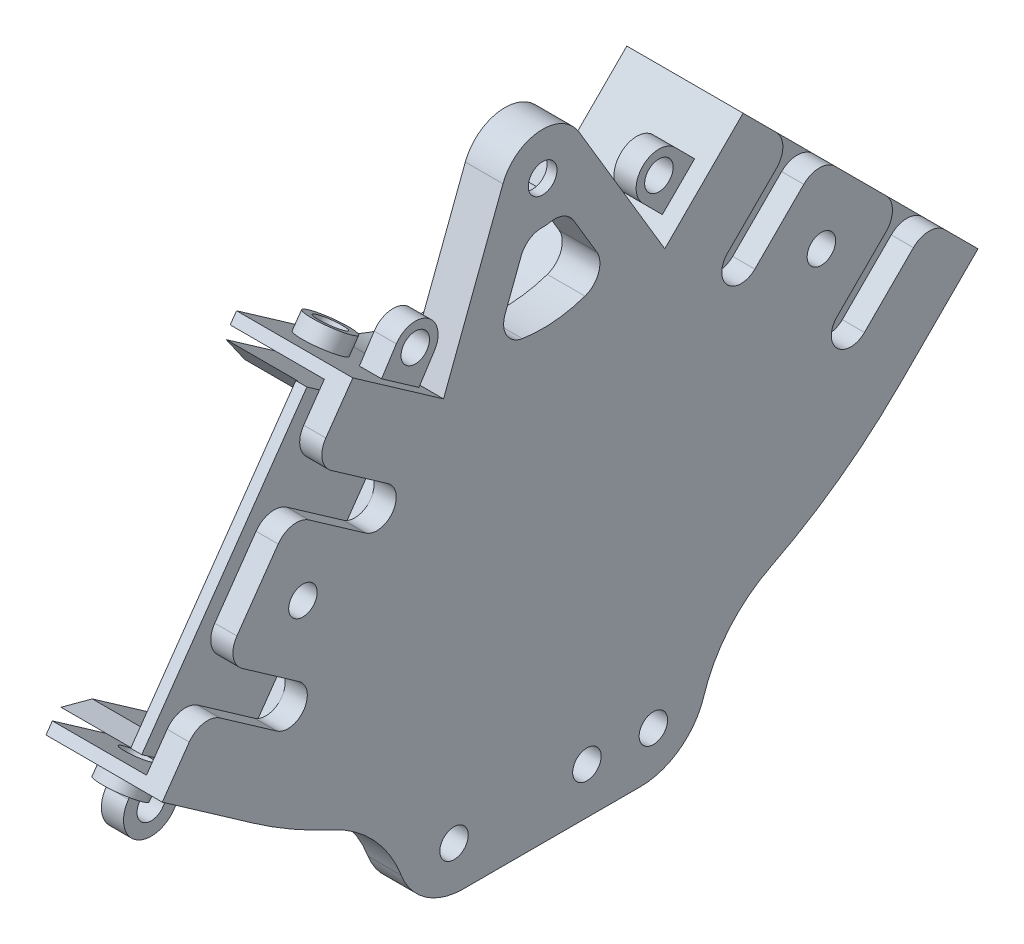
SolidWorks part; units mm, degrees
ref_plane "Front Plane" through (0, 0, 0) normal (0, 0, 1) x (1, 0, 0)
ref_plane "Top Plane" through (0, 0, 0) normal (0, 1, 0) x (1, 0, 0)
ref_plane "Right Plane" through (0, 0, 0) normal (1, 0, 0) x (0, 0, -1)
sketch "Sketch3" plane through (0, 0, 0) normal (1, 0, 0) x (0, 0, -1)
  line L0 (-22.7274, -32.4581) -> (-62.0633, -88.6355)
  line L1 (28.0184, -28.0184) -> (76.5118, -76.5118)
  line L2 (-22.7274, -32.4581) -> (0, 0) construction
  line L3 (0, 0) -> (28.0184, -28.0184) construction
  line L4 (0, 40.513) -> (0, -40.513) construction
  line L5 (-62.0633, -88.6355) -> (-66.4339, -94.8775)
  line L6 (76.5118, -76.5118) -> (81.8999, -81.8999)
  arc A2 (-62.0633, -88.6355) -> (76.5118, -76.5118) centre (0, 0) ccw
  arc A4 (-27.098, -38.7) -> (33.4066, -33.4066) centre (0, 0) ccw
  arc A5 (-22.7274, -32.4581) -> (28.0184, -28.0184) centre (0, 0) ccw
  arc A6 (-66.4339, -94.8775) -> (81.8999, -81.8999) centre (0, 0) ccw
  dimension "D1" = 216.408
  dimension "D2" = 135
  dimension "D3" = 94.488
  dimension "D4" = 7.62
  dimension "D6" = 7.62
  dimension "D5" = 80
extrude "Base extrude" add sketch "Sketch3" along normal blind 58.42 contours L5 A6 L6 A2 | A5 L0 A4 L1 region at (0, -39.9408, -3.4944) region at (0, -109.321, -9.5643)
sketch "Sketch4" plane through (58.42, 0, 0) normal (1, 0, 0) x (0, 0, -1)
  line L0 (-66.4339, -94.8775) -> (-22.7274, -32.4581)
  line L1 (28.0184, -28.0184) -> (81.8999, -81.8999)
  arc A0 (-22.7274, -32.4581) -> (28.0184, -28.0184) centre (0, 0) ccw
  arc A1 (-22.7274, -32.4581) -> (28.0184, -28.0184) centre (0, 0) ccw construction
  arc A2 (-66.4339, -94.8775) -> (81.8999, -81.8999) centre (0, 0) ccw
  arc A3 (-66.4339, -94.8775) -> (81.8999, -81.8999) centre (0, 0) ccw construction
  arc M1 (28.0184, -28.0184) -> (-22.7274, -32.4581) centre (0, 0) cw
  line M2 (-22.7274, -32.4581) -> (-27.098, -38.7)
  arc M3 (-27.098, -38.7) -> (33.4066, -33.4066) centre (0, 0) ccw
  line M4 (33.4066, -33.4066) -> (28.0184, -28.0184)
extrude "Outer wall" add sketch "Sketch4" along normal blind 7.62 contours L0 A2 L1 M3 | M4 M1 M2 M3 region at (58.42, -79.1939, -6.9286) region at (58.42, -39.9408, -3.4944)
ref_plane "Midplane" through (29.21, 0, 0) normal (-1, 0, 0) x (0, 0, 1)
mirror "Mirror1" about plane through (29.21, 0, 0) normal (-1, 0, 0) of "Outer wall"
sketch "Sketch6" plane through (0, 0, 0) normal (0, 0.5736, 0.8192) x (1, 0, 0)
  line L27 (-5.08, -42.164) -> (63.5, -42.164)
  line L28 (-5.08, -42.164) -> (-5.08, -113.284)
  line L29 (-5.08, -113.284) -> (63.5, -113.284)
  line L30 (63.5, -42.164) -> (63.5, -113.284)
  line L31 (-2.54, -44.704) -> (60.96, -44.704)
  line L32 (-2.54, -44.704) -> (-2.54, -110.744)
  line L33 (-2.54, -110.744) -> (60.96, -110.744)
  line L34 (60.96, -44.704) -> (60.96, -110.744)
  line L35 (58.42, -47.244) -> (0, -47.244) construction
  line L36 (0, -108.204) -> (0, -18.7894) construction
  line L37 (58.42, -18.7894) -> (58.42, -108.204) construction
  line L38 (58.42, -108.204) -> (0, -108.204) construction
  line L40 (0, -47.244) -> (58.42, -47.244)
  line L41 (0, -47.244) -> (0, -108.204)
  line L42 (0, -108.204) -> (58.42, -108.204)
  line L43 (58.42, -47.244) -> (58.42, -108.204)
  line L44 (-7.62, -39.624) -> (66.04, -39.624)
  line L45 (-7.62, -39.624) -> (-7.62, -115.824)
  line L46 (-7.62, -115.824) -> (66.04, -115.824)
  line L47 (66.04, -39.624) -> (66.04, -115.824)
  line M21 (-7.62, -39.624) -> (-7.62, -115.824)
  line M22 (-7.62, -115.824) -> (66.04, -115.824)
  line M23 (66.04, -115.824) -> (66.04, -39.624)
  line M24 (66.04, -39.624) -> (-7.62, -39.624)
  line M25 (58.42, -108.204) -> (0, -108.204)
  line M26 (0, -108.204) -> (0, -47.244)
  line M27 (0, -47.244) -> (58.42, -47.244)
  line M28 (58.42, -47.244) -> (58.42, -108.204)
  dimension "D1" = 2.54
  dimension "D2" = 2.54
  dimension "D3" = 2.54
  dimension "D4" = 2.54
  dimension "D5" = 2.54
  dimension "D6" = 2.54
  dimension "D7" = 2.54
  dimension "D8" = 2.54
extrude "Endcap 1" add sketch "Sketch6" along normal blind 25.4 contours L27 L30 L29 L28 M24 M21 M22 M23 | L34 L31 L32 L33 M28 M25 M26 M27 region at (29.21, -37.3698, 26.1667) region at (29.21, -33.3262, 23.3353)
sketch "Sketch7" plane through (0, 0, 0) normal (0, 0.7071, -0.7071) x (1, 0, 0)
  line L0 (-5.08, 113.284) -> (63.5, 113.284)
  line L1 (-5.08, 113.284) -> (-5.08, 42.164)
  line L2 (-5.08, 42.164) -> (63.5, 42.164)
  line L3 (63.5, 113.284) -> (63.5, 42.164)
  line L4 (-2.54, 110.744) -> (60.96, 110.744)
  line L5 (-2.54, 110.744) -> (-2.54, 44.704)
  line L6 (-2.54, 44.704) -> (60.96, 44.704)
  line L7 (60.96, 110.744) -> (60.96, 44.704)
  line L8 (0, 108.204) -> (58.42, 108.204)
  line L9 (0, 108.204) -> (0, 47.244)
  line L10 (0, 47.244) -> (58.42, 47.244)
  line L11 (58.42, 108.204) -> (58.42, 47.244)
  line L12 (-7.62, 115.824) -> (66.04, 115.824)
  line L13 (-7.62, 115.824) -> (-7.62, 39.624)
  line L14 (-7.62, 39.624) -> (66.04, 39.624)
  line L15 (66.04, 115.824) -> (66.04, 39.624)
  line L16 (58.42, 108.204) -> (0, 108.204) construction
  line L17 (58.42, 47.244) -> (58.42, 108.204) construction
  line L18 (66.04, 115.824) -> (-7.62, 115.824) construction
  line L19 (66.04, 39.624) -> (66.04, 115.824) construction
  line L20 (-7.62, 39.624) -> (-7.62, 115.824) construction
  line L21 (66.04, 39.624) -> (-7.62, 39.624) construction
  line M17 (66.04, 115.824) -> (-7.62, 115.824)
  line M18 (-7.62, 115.824) -> (-7.62, 39.624)
  line M19 (-7.62, 39.624) -> (66.04, 39.624)
  line M20 (66.04, 39.624) -> (66.04, 115.824)
  line M21 (0, 47.244) -> (0, 108.204)
  line M22 (0, 108.204) -> (58.42, 108.204)
  line M23 (58.42, 108.204) -> (58.42, 47.244)
  line M24 (58.42, 47.244) -> (0, 47.244)
  dimension "D1" = 2.54
  dimension "D2" = 2.54
  dimension "D3" = 2.54
  dimension "D4" = 2.54
  dimension "D5" = 2.54
  dimension "D6" = 2.54
  dimension "D7" = 2.54
  dimension "D8" = 2.54
extrude "Endcap 2" add sketch "Sketch7" along normal blind 25.4 contours L0 L3 L2 L1 M20 M17 M18 M19 | L7 L4 L5 L6 M24 M21 M22 M23 region at (29.21, -77.66, -77.66) region at (29.21, -81.1505, -81.1505)
chamfer "Internal Chamfer" distance 7.62 angle 20 4 edges at (29.21, -74.0667, 82.8697) (29.21, -24.1312, 47.9045) (29.21, -58.5513, -94.4723) (29.21, -15.446, -51.3671) first distance on face at (29.21, -81.3511, 72.4665) first distance on face at (29.21, -31.4156, 37.5013) first distance on face at (29.21, -67.5315, -85.492) first distance on face at (29.21, -24.4263, -42.3868)
ref_plane "Plane2" through (0, -13.9736, -1.2225) normal (0, -0.9962, -0.0872) x (-1, 0, 0)
sketch "Sketch10" plane through (0, -13.9736, -1.2225) normal (0, -0.9962, -0.0872) x (-1, 0, 0)
  line L0 (-66.04, 93.9078) -> (7.62, 93.9078) construction
  line L1 (-16.51, 95.5358) -> (-41.91, 95.5358)
  line L2 (-16.51, 95.5358) -> (-16.51, -82.1857)
  line L3 (-16.51, -82.1857) -> (-41.91, -82.1857)
  line L4 (-41.91, 95.5358) -> (-41.91, -82.1857)
  point P4 (-29.21, 93.9078)
  point P5 (-29.21, 95.5358)
  dimension "D1" = 25.4
extrude "Flywheel Hole" cut sketch "Sketch10" along normal up to next
sketch "Sketch11" plane through (-7.62, 0, 0) normal (-1, 0, 0) x (0, 0, 1)
  line L0 (-25.2982, 2.2719) -> (-28.0184, -28.0184)
  line L4 (-3.0636, -22.3183) -> (-4.5937, -39.3568)
  line L5 (6.8995, -21.445) -> (11.3704, -37.9575)
  line L6 (-20.4217, -1.79) -> (20.4217, 1.79) construction
  line L7 (24.5172, 6.6383) -> (33.1306, -25.1737)
  line L8 (43.5339, -17.8892) -> (22.7274, -32.4581) construction
  line L10 (1.5525, -17.7121) -> (-2.2178, 25.303) construction
  line L11 (22.7274, -32.4581) -> (43.5339, -17.8892)
  line L12 (22.7274, -32.4581) -> (33.1306, -25.1737)
  arc A1 (-28.0184, -28.0184) -> (22.7274, -32.4581) centre (0, 0) ccw construction
  circle A3 centre (0, 0) radius 4.064
  arc A4 (24.5172, 6.6383) -> (-25.2982, 2.2719) centre (0, 0) ccw
  circle A6 centre (-20.4217, -1.79) radius 2.5
  circle A7 centre (20.4217, 1.79) radius 2.5
  arc A8 (-3.0636, -22.3183) -> (6.8995, -21.445) centre (1.9961, -22.7727) cw
  arc A11 (11.3704, -37.9575) -> (22.7274, -32.4581) centre (0, 0) ccw
  arc A12 (-28.0184, -28.0184) -> (22.7274, -32.4581) centre (0, 0) ccw
  arc A13 (-28.0184, -28.0184) -> (-4.5937, -39.3568) centre (0, 0) ccw
  point P22 (0, 0)
  dimension "D3" = 8.128
  dimension "D2" = 25.4
  dimension "D1" = 5
  dimension "D5" = 5.08
  dimension "D4" = 41
  dimension "D7" = 43.18
  dimension "D6" = 0
extrude "Flywheel holder" add sketch "Sketch11" against normal blind 7.62
sketch "Sketch12" plane through (-7.62, 0, 0) normal (-1, 0, 0) x (0, 0, 1)
  circle A0 centre (0, 0) radius 14.605
  dimension "D1" = 29.21
extrude "Motor insert" cut sketch "Sketch12" against normal blind 6.35
sketch "Sketch14" plane through (-7.62, 0, 0) normal (-1, 0, 0) x (0, 0, 1)
  line L1 (-106.5763, 40.9543) -> (105.556, 40.9543)
  line L2 (-106.5763, 40.9543) -> (-106.5763, -120.0185)
  line L3 (-106.5763, -120.0185) -> (105.556, -120.0185)
  line L4 (105.556, 40.9543) -> (105.556, -120.0185)
extrude "Cut-Extrude2" cut sketch "Sketch14" against normal up to surface (49.53 mm away) up to face at (41.91, -26.9401, -2.3569)
sketch "Sketch15" plane through (41.91, 0, 0) normal (-1, 0, 0) x (0, 0, 1)
  line L0 (-93.8083, -77.7308) -> (-89.6212, -74.1787)
  line L1 (-99.8604, -63.9394) -> (-81.8999, -81.8999) construction
  line L2 (-89.6212, -74.1787) -> (-80.6312, -83.1493)
  line L3 (-80.6312, -83.1493) -> (-85.0539, -86.9012)
  line L4 (-16.51, -121.4959) -> (-16.51, -114.6413)
  line L5 (-16.51, -114.6413) -> (-3.8593, -115.7597)
  line L6 (-3.8593, -115.7597) -> (-3.8593, -120.7059)
  line L7 (63.1155, -104.8839) -> (59.3284, -99.4753)
  line L8 (59.3284, -99.4753) -> (69.9059, -92.4464)
  line L9 (66.4339, -94.8775) -> (87.2404, -80.3086) construction
  line L10 (69.9059, -92.4464) -> (73.4123, -97.454)
  circle A0 centre (-89.7004, -82.5731) radius 3.2639
  circle A1 centre (-10.16, -121.4959) radius 3.2639
  circle A2 centre (68.1904, -101.0671) radius 3.2639
  arc A3 (-93.8083, -77.7308) -> (-85.0539, -86.9012) centre (-89.7004, -82.5731) ccw
  arc A5 (62.868, -104.5305) -> (73.3715, -97.3959) centre (68.1904, -101.0671) ccw
  arc A6 (-81.8999, -81.8999) -> (66.4339, -94.8775) centre (0, 0) ccw construction
  arc A7 (-16.51, -121.4959) -> (-3.8593, -120.7059) centre (-10.16, -121.4959) ccw
  line M28 (-99.8604, -63.9394) -> (-81.8999, -81.8999)
  arc M29 (-81.8999, -81.8999) -> (66.4339, -94.8775) centre (0, 0) ccw
  line M30 (66.4339, -94.8775) -> (87.2404, -80.3086)
  dimension "D4" = 6.5278
  dimension "D5" = 12.7
  dimension "D1" = 121.92
  dimension "D2" = 121.92
  dimension "D3" = 121.92
  dimension "D6" = 10.16
  dimension "D7" = 10.16
  dimension "D8" = 19.05
  dimension "D9" = 12.7
  dimension "D10" = 12.7
  dimension "D11" = 12.7
extrude "Joining screw holes" add sketch "Sketch15" against normal blind 5.08 contours L0 A3 L3 A0 M29 M28 | L4 A7 L6 A1 M29 | L7 A5 L10 A2 M30 M29 region at (41.91, -97.4205, 63.0391) region at (41.91, -115.5565, -10.2161) region at (41.91, -76.1174, -91.5767)
ref_plane "Plane3" through (59.69, 0, 0) normal (1, 0, 0) x (0, 0, -1)
sketch "Sketch16" plane through (59.69, 0, 0) normal (1, 0, 0) x (0, 0, -1)
  line L0 (-43.5339, -17.8892) -> (-22.7274, -32.4581) construction
  line L1 (45.9789, -10.0579) -> (28.0184, -28.0184) construction
  line L2 (-29.7459, -19.9251) -> (-33.1306, -25.1737)
  line L3 (-33.1306, -25.1737) -> (-24.5641, -31.172)
  line L4 (-24.5641, -31.172) -> (-21.1794, -25.9235)
  line L5 (26.7818, -20.2747) -> (31.2719, -24.7649)
  line L6 (31.2719, -24.7649) -> (38.6683, -17.3685)
  line L7 (38.6683, -17.3685) -> (34.1782, -12.8783)
  line L8 (34.1782, -12.8783) -> (26.7818, -20.2747) construction
  circle A0 centre (-25.4, -22.8348) radius 3.2639
  circle A1 centre (30.48, -16.5765) radius 3.2639
  arc A2 (-21.1794, -25.9235) -> (-29.8435, -20.0764) centre (-25.4, -22.8348) ccw
  arc A3 (34.1782, -12.8783) -> (26.7818, -20.2747) centre (30.48, -16.5765) ccw
  dimension "D3" = 6.5278
  dimension "D1" = 6.35
  dimension "D2" = 6.35
  dimension "D4" = 25.4
  dimension "D5" = 30.48
  dimension "D6" = 55.88
  dimension "D7" = 6.2582
extrude "Flywheel cover connectors" add sketch "Sketch16" along normal blind 5.08 contours L4 A2 L2 L3 A0 | L7 L8 A1 L5 L6 | L8 A3 A1 region at (59.69, -18.7043, 22.5078) region at (59.69, -19.2478, -33.1513) region at (59.69, -12.9676, -26.8711)
sketch "Sketch17" plane through (66.04, 0, 0) normal (1, 0, 0) x (0, 0, -1)
  line L0 (-30.48, -111.7415) -> (-30.48, -132.08)
  line L1 (-30.48, -132.08) -> (35.56, -132.08)
  line L2 (35.56, -132.08) -> (35.56, -110.2301)
  circle A0 centre (-20.32, -121.92) radius 3.2639
  circle A1 centre (25.4, -121.92) radius 3.2639
  arc A2 (-66.4339, -94.8775) -> (81.8999, -81.8999) centre (0, 0) ccw construction
  circle A4 centre (10.16, -121.4959) radius 3.2639
  arc A5 (-66.4339, -94.8775) -> (81.8999, -81.8999) centre (0, 0) ccw
  arc A6 (-30.48, -111.7415) -> (35.56, -110.2301) centre (0, 0) ccw
  circle A7 centre (10.16, -121.4959) radius 3.2639 construction
  dimension "D1" = 6.5278
  dimension "D2" = 20.32
  dimension "D3" = 25.4
  dimension "D4" = 121.92
  dimension "D5" = 0
  dimension "D6" = 10.16
  dimension "D7" = 10.16
  dimension "D8" = 10.16
extrude "80-20 connector" add sketch "Sketch17" against normal blind 5.08
fillet "Fillet1" radius 30.48 2 edges at (63.5, -111.7415, 30.48) (63.5, -110.2301, -35.56)
fillet "Fillet2" radius 15.24 2 edges at (63.5, -132.08, -35.56) (63.5, -132.08, 30.48)
sketch "Sketch18" plane through (66.04, 0, 0) normal (1, 0, 0) x (0, 0, -1)
  line L0 (-35.474, -42.9126) -> (-52.6394, -30.8933)
  line L1 (-87.2404, -80.3086) -> (-43.5339, -17.8892) construction
  line L2 (-52.6394, -30.8933) -> (-57.7385, -38.1755)
  line L3 (-57.7385, -38.1755) -> (-40.5731, -50.1948)
  line L4 (-55.8704, -72.0416) -> (-73.0358, -60.0223)
  line L5 (-73.0358, -60.0223) -> (-78.1349, -67.3046)
  line L6 (-78.1349, -67.3046) -> (-60.9695, -79.3239)
  line L7 (42.3868, -36.1006) -> (57.2042, -21.2832)
  line L8 (45.9789, -10.0579) -> (99.8604, -63.9394) construction
  line L9 (57.2042, -21.2832) -> (63.4904, -27.5694)
  line L10 (63.4904, -27.5694) -> (48.673, -42.3868)
  line L11 (67.5315, -61.2453) -> (82.3489, -46.4279)
  line L12 (82.3489, -46.4279) -> (88.6351, -52.7141)
  line L13 (88.6351, -52.7141) -> (73.8177, -67.5315)
  line L14 (-43.5339, -17.8892) -> (-22.7274, -32.4581) construction
  line L15 (45.9789, -10.0579) -> (28.0184, -28.0184) construction
  line L16 (99.8604, -63.9394) -> (81.8999, -81.8999) construction
  line L17 (-87.2404, -80.3086) -> (-66.4339, -94.8775) construction
  line L18 (-24.1843, -34.5387) -> (-64.977, -92.7968) construction
  arc A0 (-40.5731, -50.1948) -> (-35.474, -42.9126) centre (-38.0236, -46.5537) ccw
  arc A1 (-60.9695, -79.3239) -> (-55.8704, -72.0416) centre (-58.42, -75.6827) ccw
  arc A2 (42.3868, -36.1006) -> (48.673, -42.3868) centre (45.5299, -39.2437) ccw
  arc A3 (67.5315, -61.2453) -> (73.8177, -67.5315) centre (70.6746, -64.3884) ccw
  dimension "D1" = 8.89
  dimension "D3" = 20.32
  dimension "D4" = 20.32
  dimension "D5" = 20.32
  dimension "D6" = 20.32
extrude "Support Removal" cut sketch "Sketch18" against normal up to next
fillet "Fillet3" radius 5.08 8 edges at (64.77, -52.7141, -88.6351) (64.77, -46.4279, -82.3489) (64.77, -27.5694, -63.4904) (64.77, -21.2832, -57.2042) (64.77, -67.3046, 78.1349) (64.77, -60.0223, 73.0358) (64.77, -38.1755, 57.7385) (64.77, -30.8933, 52.6394)
sketch "Sketch19" plane through (66.04, 0, 0) normal (1, 0, 0) x (0, 0, -1)
  line L0 (-70.122, -55.861) -> (-60.6522, -42.3368) construction
  line L1 (67.0825, -31.1615) -> (78.7568, -42.8358) construction
  line L2 (-65.3871, -49.0989) -> (-54.9839, -56.3834) construction
  line L3 (-34.3825, -49.1033) -> (-54.7788, -78.2323) construction
  line L4 (67.5315, -67.5315) -> (42.3868, -42.3868) construction
  line L5 (72.9197, -36.9987) -> (63.9394, -45.9789) construction
  circle A0 centre (-54.9839, -56.3834) radius 3.2639
  circle A1 centre (63.9394, -45.9789) radius 3.2639
  point P4 (-65.3871, -49.0989)
  point P5 (72.9197, -36.9987)
  dimension "D1" = 6.5278
  dimension "D2" = 12.7
  dimension "D3" = 12.7
extrude "Cut-Extrude3" cut sketch "Sketch19" against normal up to next contours A1 | A0 region at (66.04, -56.3834, 54.9839) region at (66.04, -45.9789, -63.9394)
sketch "Sketch20" plane through (0, -94.8775, 66.4339) normal (0, -0.8192, 0.5736) x (1, 0, 0)
  line L0 (63.5, 25.4) -> (63.5, 0) construction
  line L1 (41.91, 0) -> (63.5, 0) construction
  circle A0 centre (50.8, 12.7) radius 3.2639
  dimension "D1" = 6.5278
  dimension "D2" = 12.7
  dimension "D3" = 12.7
extrude "Cut-Extrude4" cut sketch "Sketch20" against normal up to next
ref_plane "Plane4" through (0, -63.6678, 44.5807) normal (0, 0.8192, -0.5736) x (1, 0, 0)
mirror "Mirror2" about plane through (0, -63.6678, 44.5807) normal (0, 0.8192, -0.5736) of "Cut-Extrude4"
sketch "Sketch21" plane through (0, -81.8999, -81.8999) normal (0, -0.7071, -0.7071) x (1, 0, 0)
  line L0 (66.04, 0) -> (46.99, 0) construction
  line L1 (63.5, -25.4) -> (63.5, 0) construction
  circle A0 centre (50.8, -12.7) radius 3.2639
  dimension "D1" = 6.5278
  dimension "D2" = 12.7
  dimension "D3" = 12.7
extrude "Cut-Extrude5" cut sketch "Sketch21" against normal up to next contours A0
sketch "Sketch22" plane through (66.04, 0, 0) normal (1, 0, 0) x (0, 0, -1)
  line L38 (99.8604, -63.9394) -> (92.2272, -56.3062)
  line L39 (85.043, -56.3062) -> (73.8177, -67.5315)
  line L40 (67.5315, -61.2453) -> (78.7568, -50.02)
  line L41 (78.7568, -42.8358) -> (67.0825, -31.1615)
  line L42 (59.8983, -31.1615) -> (48.673, -42.3868)
  line L43 (42.3868, -36.1006) -> (53.6121, -24.8753)
  line L44 (53.6121, -17.6911) -> (45.9789, -10.0579)
  line L45 (45.9789, -10.0579) -> (28.0184, -28.0184)
  line L46 (-22.7274, -32.4581) -> (-43.5339, -17.8892)
  line L47 (-43.5339, -17.8892) -> (-49.7256, -26.732)
  line L48 (-48.4781, -33.807) -> (-35.474, -42.9126)
  line L49 (-40.5731, -50.1948) -> (-53.5772, -41.0893)
  line L50 (-60.6522, -42.3368) -> (-70.122, -55.861)
  line L51 (-68.8745, -62.9361) -> (-55.8704, -72.0416)
  line L52 (-60.9695, -79.3239) -> (-73.9736, -70.2184)
  line L53 (-81.0486, -71.4659) -> (-87.2404, -80.3086)
  line L54 (-87.2404, -80.3086) -> (-66.4339, -94.8775)
  line L55 (-18.1792, -132.08) -> (22.4243, -132.08)
  line L56 (81.8999, -81.8999) -> (99.8604, -63.9394)
  line L57 (99.8604, -63.9394) -> (92.2272, -56.3062)
  line L58 (85.043, -56.3062) -> (73.8177, -67.5315)
  line L59 (67.5315, -61.2453) -> (78.7568, -50.02)
  line L60 (78.7568, -42.8358) -> (67.0825, -31.1615)
  line L61 (59.8983, -31.1615) -> (48.673, -42.3868)
  line L62 (42.3868, -36.1006) -> (53.6121, -24.8753)
  line L63 (53.6121, -17.6911) -> (45.9789, -10.0579)
  line L64 (45.9789, -10.0579) -> (28.0184, -28.0184)
  line L65 (-22.7274, -32.4581) -> (-43.5339, -17.8892)
  line L66 (-43.5339, -17.8892) -> (-49.7256, -26.732)
  line L67 (-48.4781, -33.807) -> (-35.474, -42.9126)
  line L68 (-40.5731, -50.1948) -> (-53.5772, -41.0893)
  line L69 (-60.6522, -42.3368) -> (-70.122, -55.861)
  line L70 (-68.8745, -62.9361) -> (-55.8704, -72.0416)
  line L71 (-60.9695, -79.3239) -> (-73.9736, -70.2184)
  line L72 (-81.0486, -71.4659) -> (-87.2404, -80.3086)
  line L73 (-87.2404, -80.3086) -> (-66.4339, -94.8775)
  line L74 (-18.1792, -132.08) -> (22.4243, -132.08)
  line L75 (81.8999, -81.8999) -> (99.8604, -63.9394)
  circle A21 centre (-54.9839, -56.3834) radius 3.2639
  circle A22 centre (-54.9839, -56.3834) radius 3.2639
  circle A24 centre (-20.32, -121.92) radius 3.2639
  circle A25 centre (-20.32, -121.92) radius 3.2639
  circle A27 centre (10.16, -121.4959) radius 3.2639
  circle A28 centre (10.16, -121.4959) radius 3.2639
  circle A30 centre (25.4, -121.92) radius 3.2639
  circle A31 centre (25.4, -121.92) radius 3.2639
  circle A33 centre (63.9394, -45.9789) radius 3.2639
  circle A34 centre (63.9394, -45.9789) radius 3.2639
  arc A38 (92.2272, -56.3062) -> (85.043, -56.3062) centre (88.6351, -59.8983) ccw
  arc A39 (67.5315, -61.2453) -> (73.8177, -67.5315) centre (70.6746, -64.3884) ccw
  arc A40 (78.7568, -50.02) -> (78.7568, -42.8358) centre (75.1647, -46.4279) ccw
  arc A41 (67.0825, -31.1615) -> (59.8983, -31.1615) centre (63.4904, -34.7536) ccw
  arc A42 (42.3868, -36.1006) -> (48.673, -42.3868) centre (45.5299, -39.2437) ccw
  arc A43 (53.6121, -24.8753) -> (53.6121, -17.6911) centre (50.02, -21.2832) ccw
  arc A44 (-22.7274, -32.4581) -> (28.0184, -28.0184) centre (0, 0) ccw
  arc A45 (-49.7256, -26.732) -> (-48.4781, -33.807) centre (-45.5643, -29.6458) ccw
  arc A46 (-40.5731, -50.1948) -> (-35.474, -42.9126) centre (-38.0236, -46.5537) ccw
  arc A47 (-53.5772, -41.0893) -> (-60.6522, -42.3368) centre (-56.491, -45.2506) ccw
  arc A48 (-70.122, -55.861) -> (-68.8745, -62.9361) centre (-65.9607, -58.7748) ccw
  arc A49 (-60.9695, -79.3239) -> (-55.8704, -72.0416) centre (-58.42, -75.6827) ccw
  arc A50 (-73.9736, -70.2184) -> (-81.0486, -71.4659) centre (-76.8873, -74.3796) ccw
  arc A51 (-66.4339, -94.8775) -> (-48.2489, -105.296) centre (0, 0) ccw
  arc A52 (-32.4348, -122.2285) -> (-48.2489, -105.296) centre (-60.9459, -133.0055) ccw
  arc A53 (-32.4348, -122.2285) -> (-18.1792, -132.08) centre (-18.1792, -116.84) ccw
  arc A54 (22.4243, -132.08) -> (36.9629, -121.4104) centre (22.4243, -116.84) ccw
  arc A55 (52.2817, -103.3529) -> (36.9629, -121.4104) centre (66.04, -130.5511) ccw
  arc A56 (52.2817, -103.3529) -> (81.8999, -81.8999) centre (0, 0) ccw
  arc A57 (92.2272, -56.3062) -> (85.043, -56.3062) centre (88.6351, -59.8983) ccw
  arc A58 (67.5315, -61.2453) -> (73.8177, -67.5315) centre (70.6746, -64.3884) ccw
  arc A59 (78.7568, -50.02) -> (78.7568, -42.8358) centre (75.1647, -46.4279) ccw
  arc A60 (67.0825, -31.1615) -> (59.8983, -31.1615) centre (63.4904, -34.7536) ccw
  arc A61 (42.3868, -36.1006) -> (48.673, -42.3868) centre (45.5299, -39.2437) ccw
  arc A62 (53.6121, -24.8753) -> (53.6121, -17.6911) centre (50.02, -21.2832) ccw
  arc A63 (-22.7274, -32.4581) -> (28.0184, -28.0184) centre (0, 0) ccw
  arc A64 (-49.7256, -26.732) -> (-48.4781, -33.807) centre (-45.5643, -29.6458) ccw
  arc A65 (-40.5731, -50.1948) -> (-35.474, -42.9126) centre (-38.0236, -46.5537) ccw
  arc A66 (-53.5772, -41.0893) -> (-60.6522, -42.3368) centre (-56.491, -45.2506) ccw
  arc A67 (-70.122, -55.861) -> (-68.8745, -62.9361) centre (-65.9607, -58.7748) ccw
  arc A68 (-60.9695, -79.3239) -> (-55.8704, -72.0416) centre (-58.42, -75.6827) ccw
  arc A69 (-73.9736, -70.2184) -> (-81.0486, -71.4659) centre (-76.8873, -74.3796) ccw
  arc A70 (-66.4339, -94.8775) -> (-48.2489, -105.296) centre (0, 0) ccw
  arc A71 (-32.4348, -122.2285) -> (-48.2489, -105.296) centre (-60.9459, -133.0055) ccw
  arc A72 (-32.4348, -122.2285) -> (-18.1792, -132.08) centre (-18.1792, -116.84) ccw
  arc A73 (22.4243, -132.08) -> (36.9629, -121.4104) centre (22.4243, -116.84) ccw
  arc A74 (52.2817, -103.3529) -> (36.9629, -121.4104) centre (66.04, -130.5511) ccw
  arc A75 (52.2817, -103.3529) -> (81.8999, -81.8999) centre (0, 0) ccw
  circle M44 centre (63.9394, -45.9789) radius 3.2639
  circle M45 centre (-54.9839, -56.3834) radius 3.2639
  line M46 (99.8604, -63.9394) -> (92.2272, -56.3062)
  arc M47 (92.2272, -56.3062) -> (85.043, -56.3062) centre (88.6351, -59.8983) ccw
  line M48 (85.043, -56.3062) -> (73.8177, -67.5315)
  arc M49 (73.8177, -67.5315) -> (67.5315, -61.2453) centre (70.6746, -64.3884) cw
  line M50 (67.5315, -61.2453) -> (78.7568, -50.02)
  arc M51 (78.7568, -50.02) -> (78.7568, -42.8358) centre (75.1647, -46.4279) ccw
  line M52 (78.7568, -42.8358) -> (67.0825, -31.1615)
  arc M53 (67.0825, -31.1615) -> (59.8983, -31.1615) centre (63.4904, -34.7536) ccw
  line M54 (59.8983, -31.1615) -> (48.673, -42.3868)
  arc M55 (48.673, -42.3868) -> (42.3868, -36.1006) centre (45.5299, -39.2437) cw
  line M56 (42.3868, -36.1006) -> (53.6121, -24.8753)
  arc M57 (53.6121, -24.8753) -> (53.6121, -17.6911) centre (50.02, -21.2832) ccw
  line M58 (53.6121, -17.6911) -> (45.9789, -10.0579)
  line M59 (45.9789, -10.0579) -> (28.0184, -28.0184)
  arc M60 (28.0184, -28.0184) -> (-22.7274, -32.4581) centre (0, 0) cw
  line M61 (-22.7274, -32.4581) -> (-43.5339, -17.8892)
  line M62 (-43.5339, -17.8892) -> (-49.7256, -26.732)
  arc M63 (-49.7256, -26.732) -> (-48.4781, -33.807) centre (-45.5643, -29.6458) ccw
  line M64 (-48.4781, -33.807) -> (-35.474, -42.9126)
  arc M65 (-35.474, -42.9126) -> (-40.5731, -50.1948) centre (-38.0236, -46.5537) cw
  line M66 (-40.5731, -50.1948) -> (-53.5772, -41.0893)
  arc M67 (-53.5772, -41.0893) -> (-60.6522, -42.3368) centre (-56.491, -45.2506) ccw
  line M68 (-60.6522, -42.3368) -> (-70.122, -55.861)
  arc M69 (-70.122, -55.861) -> (-68.8745, -62.9361) centre (-65.9607, -58.7748) ccw
  line M70 (-68.8745, -62.9361) -> (-55.8704, -72.0416)
  arc M71 (-55.8704, -72.0416) -> (-60.9695, -79.3239) centre (-58.42, -75.6827) cw
  line M72 (-60.9695, -79.3239) -> (-73.9736, -70.2184)
  arc M73 (-73.9736, -70.2184) -> (-81.0486, -71.4659) centre (-76.8873, -74.3796) ccw
  line M74 (-81.0486, -71.4659) -> (-87.2404, -80.3086)
  line M75 (-87.2404, -80.3086) -> (-66.4339, -94.8775)
  arc M76 (-66.4339, -94.8775) -> (-48.2489, -105.296) centre (0, 0) ccw
  arc M77 (-48.2489, -105.296) -> (-32.4348, -122.2285) centre (-60.9459, -133.0055) cw
  arc M78 (-32.4348, -122.2285) -> (-18.1792, -132.08) centre (-18.1792, -116.84) ccw
  line M79 (-18.1792, -132.08) -> (22.4243, -132.08)
  arc M80 (22.4243, -132.08) -> (36.9629, -121.4104) centre (22.4243, -116.84) ccw
  arc M81 (36.9629, -121.4104) -> (52.2817, -103.3529) centre (66.04, -130.5511) cw
  arc M82 (52.2817, -103.3529) -> (81.8999, -81.8999) centre (0, 0) ccw
  line M83 (81.8999, -81.8999) -> (99.8604, -63.9394)
  circle M84 centre (10.16, -121.4959) radius 3.2639
  circle M85 centre (25.4, -121.92) radius 3.2639
  circle M86 centre (-20.32, -121.92) radius 3.2639
  dimension "D1" = 0
  dimension "D2" = 0
  dimension "D3" = 0
  dimension "D4" = 0
  dimension "D5" = 0
  dimension "D6" = 0
extrude "Thicken" add sketch "Sketch22" along normal blind 2.54 contours M83 M46 M47 M48 M49 M50 M51 M52 M53 M54 M55 M56 M57 M58 M59 M60 M61 M62 M63 M64 M65 M66 M67 M68 M69 M70 M71 M72 M73 M74 M75 M76 M77 M78 M79 M80 M81 M82 M45 M84 M86 M85 M44 region at (66.04, -75.2354, -5.8008)
sketch "Sketch23" plane through (68.58, 0, 0) normal (1, 0, 0) x (0, 0, -1)
  line L0 (-9.1013, 3.4534) -> (-22.7274, -32.4581)
  line L3 (8.3634, 4.9813) -> (28.0184, -28.0184)
  line L5 (-3.4534, -9.1013) -> (-10.6035, -27.9455)
  line L6 (28.0184, -28.0184) -> (45.9789, -10.0579)
  line L8 (15.2951, -25.6796) -> (15.2951, -25.6796)
  line L10 (0, 0) -> (-10.6035, -27.9455) construction
  line L11 (0, 0) -> (15.2951, -25.6796) construction
  line L12 (4.9813, -8.3634) -> (15.2951, -25.6796)
  line L19 (28.0184, -28.0184) -> (28.1487, -28.2372) construction
  line L20 (8.3634, 4.9813) -> (28.1487, -28.2372) construction
  circle A0 centre (0, 0) radius 3.302
  arc A1 (8.3634, 4.9813) -> (-9.1013, 3.4534) centre (0, 0) ccw
  arc A4 (-10.6035, -27.9455) -> (15.2951, -25.6796) centre (0, 0) ccw
  arc A5 (-22.7274, -32.4581) -> (28.0184, -28.0184) centre (0, 0) ccw
  arc A6 (-22.7274, -32.4581) -> (28.0184, -28.0184) centre (0, 0) ccw
  arc A7 (0, 0) -> (0, 0) centre (0, 0) ccw
  arc A8 (-3.4534, -9.1013) -> (4.9813, -8.3634) centre (0, 0) ccw
  arc A9 (8.3634, 4.9813) -> (-9.1013, 3.4534) centre (0, 0) ccw
  line M29 (45.9789, -10.0579) -> (28.0184, -28.0184)
  arc M30 (28.0184, -28.0184) -> (-22.7274, -32.4581) centre (0, 0) cw
  dimension "D2" = 0
extrude "Axle Holder" add sketch "Sketch23" against normal blind 8.636 contours A1 L0 A0 L5 A8 L12 A4 M30 M29 region at (68.58, 8.9922, 0.7867)
fillet "Fillet4" radius 5.08 4 edges at (64.262, -8.3634, -4.9813) (64.262, -9.1013, 3.4534) (64.262, -25.6796, -15.2951) (64.262, -27.9455, 10.6035)
sketch "Sketch24" plane through (59.944, 0, 0) normal (-1, 0, 0) x (0, 0, 1)
  line L6 (-3.2262, 5.588) -> (3.2262, 5.588)
  line L7 (3.2262, 5.588) -> (6.4525, 0)
  line L8 (6.4525, 0) -> (3.2262, -5.588)
  line L9 (3.2262, -5.588) -> (-3.2262, -5.588)
  line L10 (-3.2262, -5.588) -> (-6.4525, 0)
  line L11 (-6.4525, 0) -> (-3.2262, 5.588)
  line L12 (-3.2262, 5.588) -> (3.2262, -5.588) construction
  point P2 (0, 0)
  dimension "D1" = 120
  dimension "D2" = 11.176
extrude "Nut hole" cut sketch "Sketch24" against normal blind 6.35
sketch "Sketch25" plane through (0, -32.4581, 22.7274) normal (0, 0.8192, -0.5736) x (1, 0, 0)
  circle A0 centre (50.8, -12.7) radius 3.2639
  circle A1 centre (50.8, -12.7) radius 5.08
  circle A2 centre (50.8, -12.7) radius 3.2639 construction
  dimension "D1" = 10.16
extrude "Boss-Extrude1" add sketch "Sketch25" along normal blind 3.81
sketch "Sketch26" plane through (0, -94.8775, 66.4339) normal (0, -0.8192, 0.5736) x (1, 0, 0)
  circle A0 centre (50.8, 12.7) radius 3.2639
  circle A1 centre (50.8, 12.7) radius 5.08
  circle A2 centre (50.8, 12.7) radius 3.2639 construction
  dimension "D1" = 10.16
extrude "Boss-Extrude2" add sketch "Sketch26" along normal blind 3.81
